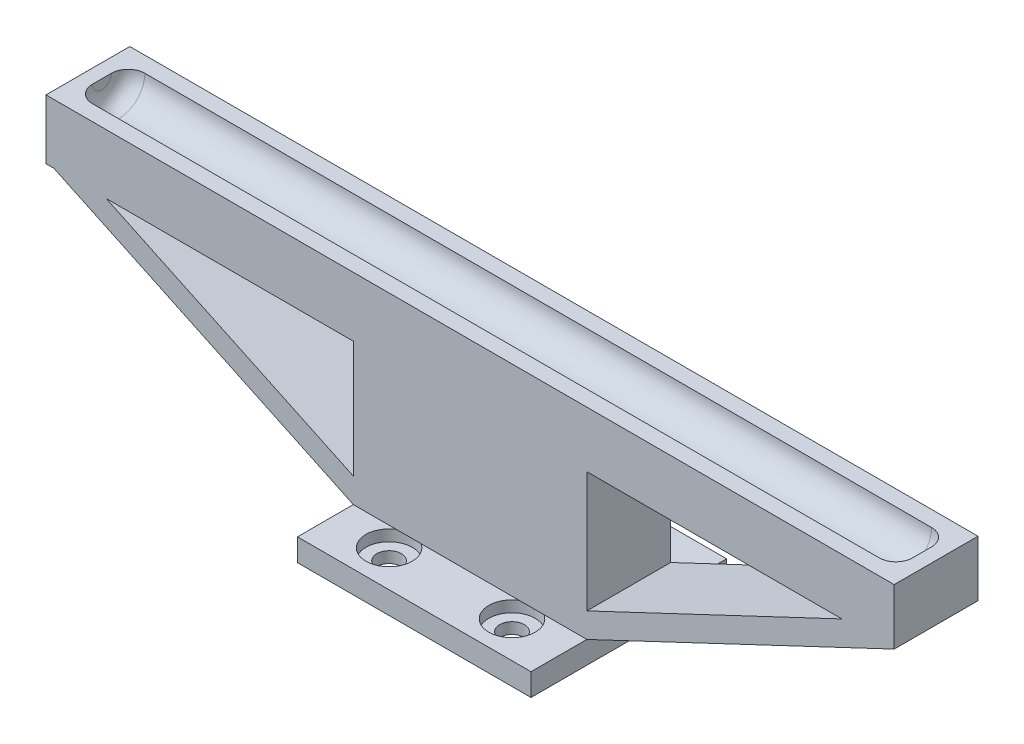
SolidWorks part; units mm, degrees
ref_plane "Front Plane" through (0, 0, 0) normal (0, 0, 1) x (1, 0, 0)
ref_plane "Top Plane" through (0, 0, 0) normal (0, 1, 0) x (1, 0, 0)
ref_plane "Right Plane" through (0, 0, 0) normal (1, 0, 0) x (0, 0, -1)
sketch "Sketch1" plane through (0, 0, 0) normal (0, 1, 0) x (1, 0, 0)
  line L8 (0, 28.0906) -> (151.8, 28.0906)
  line L9 (0, 28.0906) -> (0, 13.0906)
  line L10 (0, 13.0906) -> (151.8, 13.0906)
  line L11 (151.8, 28.0906) -> (151.8, 13.0906)
  line L22 (7.5, 20.5906) -> (144.3, 20.5906) construction
  circle A0 centre (7.5, 20.5906) radius 4.7 construction
  circle A1 centre (22.7, 20.5906) radius 4.7 construction
  circle A2 centre (37.9, 20.5906) radius 4.7 construction
  circle A3 centre (53.1, 20.5906) radius 4.7 construction
  circle A4 centre (68.3, 20.5906) radius 4.7 construction
  circle A5 centre (83.5, 20.5906) radius 4.7 construction
  circle A6 centre (98.7, 20.5906) radius 4.7 construction
  circle A7 centre (113.9, 20.5906) radius 4.7 construction
  circle A8 centre (129.1, 20.5906) radius 4.7 construction
  circle A9 centre (144.3, 20.5906) radius 4.7 construction
  circle A10 centre (15.1, 33.2906) radius 4.7 construction
  circle A11 centre (30.3, 33.2906) radius 4.7 construction
  circle A12 centre (45.5, 33.2906) radius 4.7 construction
  circle A13 centre (60.7, 33.2906) radius 4.7 construction
  circle A14 centre (75.9, 33.2906) radius 4.7 construction
  circle A15 centre (91.1, 33.2906) radius 4.7 construction
  circle A16 centre (106.3, 33.2906) radius 4.7 construction
  circle A17 centre (121.5, 33.2906) radius 4.7 construction
  circle A18 centre (136.7, 33.2906) radius 4.7 construction
  circle A19 centre (151.9, 33.2906) radius 4.7 construction
  dimension "D2" = 9.4
  dimension "D4" = 7.5
  dimension "D8" = 9.4
  dimension "D9" = 10
  dimension "D1" = 7.5
  dimension "D5" = 136.8
  dimension "D6" = 7.5
  dimension "7.5" = 7.5
  dimension "D10" = 12.7
  dimension "D11" = 7.6
  dimension "D3" = 10
extrude "Boss-Extrude1" add sketch "Sketch1" along normal blind 40
sketch "Sketch2" plane through (0, 0, -13.0906) normal (0, 0, 1) x (1, 0, 0)
  line L0 (0, 0) -> (151.8, 0) construction
  line L1 (55, 0) -> (96.8, 0)
  line L2 (55, 0) -> (55, 4)
  line L3 (55, 4) -> (96.8, 4)
  line L4 (96.8, 0) -> (96.8, 4)
  line L5 (151.8, 40) -> (151.8, 0) construction
  line L6 (0, 40) -> (0, 0) construction
  dimension "D1" = 55
  dimension "D2" = 55
  dimension "D3" = 4
extrude "Boss-Extrude2" add sketch "Sketch2" along normal blind 10
sketch "Sketch3" plane through (0, 0, 0) normal (0, -1, 0) x (1, 0, 0)
  line L0 (0, -20.5906) -> (151.8, -20.5906) construction
  line L1 (0, -28.0906) -> (0, -13.0906) construction
  line L2 (151.8, -13.0906) -> (151.8, -28.0906) construction
  line L3 (75.9, -28.0906) -> (75.9, -3.0906) construction
  line L4 (151.8, -28.0906) -> (0, -28.0906) construction
  line L5 (55, -3.0906) -> (96.8, -3.0906) construction
  circle A0 centre (86.9, -9.5906) radius 4.15
  circle A1 centre (86.9, -9.5906) radius 2.2
  circle A2 centre (64.9, -31.5906) radius 4.15 construction
  circle A3 centre (64.9, -31.5906) radius 2.2 construction
  circle A4 centre (86.9, -31.5906) radius 4.15 construction
  circle A5 centre (86.9, -31.5906) radius 2.2 construction
  circle A6 centre (64.9, -9.5906) radius 4.15
  circle A7 centre (64.9, -9.5906) radius 2.2
  dimension "D1" = 8.3
  dimension "D2" = 8.3
  dimension "D3" = 8.3
  dimension "D4" = 8.3
  dimension "D5" = 4.4
  dimension "D6" = 4.4
  dimension "D7" = 4.4
  dimension "D8" = 4.4
  dimension "D9" = 11
  dimension "D10" = 11
  dimension "D11" = 11
  dimension "D12" = 11
  dimension "D13" = 22
  dimension "D14" = 22
  dimension "D15" = 11
  dimension "D16" = 11
extrude "Cut-Extrude1" cut sketch "Sketch3" against normal blind 40 contours A7 | A1
sketch "Sketch4" plane through (0, 4, 0) normal (0, 1, 0) x (1, 0, 0)
  circle A0 centre (64.9, 9.5906) radius 4.15
  circle A1 centre (86.9, 9.5906) radius 4.15
  dimension "D1" = 8.3
  dimension "D2" = 8.3
extrude "Cut-Extrude2" cut sketch "Sketch4" against normal blind 2
sketch "Sketch5" plane through (0, 40, 0) normal (0, 1, 0) x (1, 0, 0)
  circle A0 centre (64.9, 9.5906) radius 4.15
  circle A1 centre (86.9, 9.5906) radius 4.15
sketch "Sketch6" plane through (0, 0, 0) normal (-1, 0, 0) x (0, 0, 1)
  line L1 (-28.0906, 40) -> (-13.0906, 40) construction
  circle A1 centre (-20.5906, 40) radius 4.7
  dimension "D1" = 9.4
extrude "Cut-Extrude4" cut sketch "Sketch6" against normal up to surface (151.8 mm away) up to face at (151.8, 20, -20.5906)
sketch "Sketch7" plane through (0, 40, 0) normal (0, 1, 0) x (1, 0, 0)
  line L0 (151.8, 25.2906) -> (151.8, 28.0906) construction
  line L1 (151.8, 26.6906) -> (149.3, 26.6906)
  line L2 (151.8, 26.6906) -> (151.8, 13.0906)
  line L3 (151.8, 13.0906) -> (149.3, 13.0906)
  line L4 (149.3, 26.6906) -> (149.3, 13.0906)
  line L5 (0, 13.0906) -> (151.8, 13.0906) construction
  line L6 (0, 13.0906) -> (151.8, 13.0906) construction
  line L7 (0, 28.0906) -> (2.5, 28.0906)
  line L8 (0, 28.0906) -> (0, 13.0906)
  line L9 (0, 13.0906) -> (2.5, 13.0906)
  line L10 (2.5, 28.0906) -> (2.5, 13.0906)
  dimension "D1" = 2.5
  dimension "2" = 2.5
extrude "Boss-Extrude3" add sketch "Sketch7" against normal blind 10
fillet "Fillet1" radius 3 2 edges at (149.3, 35.3, -20.5906) (2.5, 35.3, -20.5906)
ref_plane "Plane1" through (0, 0, -20.5906) normal (0, 0, 1) x (1, 0, 0)
mirror "Mirror2" about plane through (0, 0, -20.5906) normal (0, 0, 1) of "Cut-Extrude1", "Boss-Extrude2", "Cut-Extrude2"
sketch "Sketch9" plane through (0, 0, -28.0906) normal (0, 0, -1) x (-1, 0, 0)
  line L0 (-151.8, 40) -> (-151.8, 0) construction
  line L1 (-151.8, 30) -> (-96.8, 30)
  line L2 (-151.8, 30) -> (-151.8, 0)
  line L3 (-151.8, 0) -> (-96.8, 0)
  line L4 (-96.8, 30) -> (-96.8, 0)
  line L5 (0, 40) -> (0, 0) construction
  line L6 (-55, 0) -> (0, 0)
  line L7 (-55, 0) -> (-55, 29.327)
  line L8 (-55, 29.327) -> (0, 29.327)
  line L9 (0, 0) -> (0, 29.327)
  line L10 (-151.8, 40) -> (0, 40) construction
  dimension "D1" = 10
extrude "Cut-Extrude5" cut sketch "Sketch9" against normal blind 15
sketch "Sketch10" plane through (0, 0, -28.0906) normal (0, 0, -1) x (-1, 0, 0)
  line L0 (-151.8, 30) -> (-96.8, 4)
  line L1 (-150.0905, 33.6163) -> (-95.0905, 7.6163)
  line L2 (-96.8, 4) -> (-95.0905, 7.6163)
  line L3 (-150.0905, 33.6163) -> (-151.8, 30)
  line L4 (-75.9, 40) -> (-75.9, 0) construction
  line L5 (-151.8, 40) -> (0, 40) construction
  line L6 (-55, 0) -> (-96.8, 0) construction
  line L7 (-1.7095, 33.6163) -> (-56.7095, 7.6163)
  line L8 (-55, 4) -> (-56.7095, 7.6163)
  line L9 (0, 30) -> (-55, 4)
  line L10 (-1.7095, 33.6163) -> (0, 30)
  dimension "D1" = 4
extrude "Boss-Extrude4" add sketch "Sketch10" against normal up to surface (15 mm away) up to face at (75.9, 18.5545, -13.0906)
